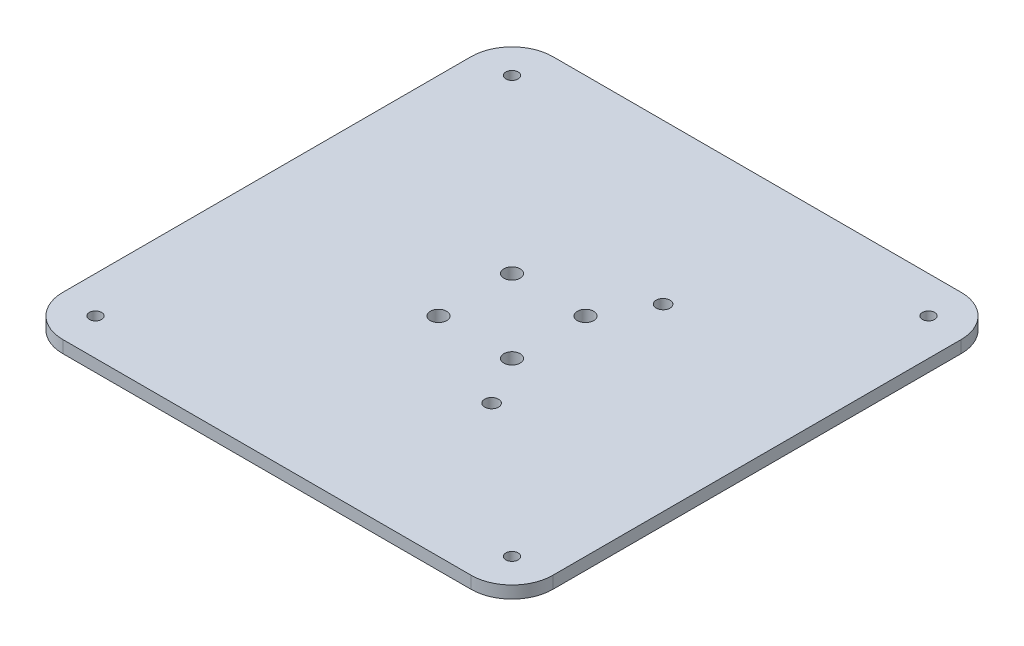
SolidWorks part; units mm, degrees
material "ABS"
ref_plane "Alzado" through (0, 0, 0) normal (0, 0, 1) x (1, 0, 0)
ref_plane "Planta" through (0, 0, 0) normal (0, 1, 0) x (1, 0, 0)
ref_plane "Vista lateral" through (0, 0, 0) normal (1, 0, 0) x (0, 0, -1)
sketch "Sketch1" plane through (0, 0, 0) normal (0, 1, 0) x (1, 0, 0)
  line L1 (-9, -9) -> (9, -9) construction
  line L2 (-9, -9) -> (-9, 9) construction
  line L3 (-9, 9) -> (9, 9) construction
  line L4 (9, -9) -> (9, 9) construction
  line L5 (-9, -9) -> (9, 9) construction
  line L6 (-9, 9) -> (9, -9) construction
  line L7 (-60, -60) -> (60, -60)
  line L8 (-60, -60) -> (-60, 60)
  line L9 (-60, 60) -> (60, 60)
  line L10 (60, -60) -> (60, 60)
  circle A0 centre (-9, -9) radius 2
  circle A1 centre (9, 9) radius 2
  circle A2 centre (9, -9) radius 2
  circle A3 centre (-9, 9) radius 2
  point P0 (0, 0)
  point P10 (0, 0)
  point P16 (-60, 0)
  point P17 (0, -60)
  dimension "D3" = 4
  dimension "D1" = 18
  dimension "D2" = 18
  dimension "D4" = 120
  dimension "D5" = 120
extrude "Boss-Extrude1" add sketch "Sketch1" along normal blind 3
fillet "Fillet1" radius 10 4 edges at (-60, 1.5, -60) (60, 1.5, -60) (60, 1.5, 60) (-60, 1.5, 60)
sketch "Sketch2" plane through (0, 3, 0) normal (0, 1, 0) x (1, 0, 0)
  line L0 (50, 60) -> (-50, 60) construction
  line L1 (-60, 50) -> (-60, -50) construction
  circle A0 centre (-51, 51) radius 1.5
  dimension "D1" = 3
  dimension "D2" = 9
  dimension "D3" = 9
extrude "Cut-Extrude1" cut sketch "Sketch2" against normal through all
mirror "Mirror3" about plane through (0, 0, 0) normal (0, 0, 1) of "Cut-Extrude1" second plane through (0, 0, 0) second plane normal (1, 0, 0)
sketch "Sketch3" plane through (0, 3, 0) normal (0, 1, 0) x (1, 0, 0)
  line L0 (16, 21) -> (16, -21) construction
  circle A2 centre (16, 21) radius 1.7
  circle A3 centre (16, -21) radius 1.7
  point P4 (16, 0)
  dimension "D2" = 42
  dimension "D1" = 3.4
  dimension "D3" = 16
extrude "Cut-Extrude2" cut sketch "Sketch3" against normal through all
